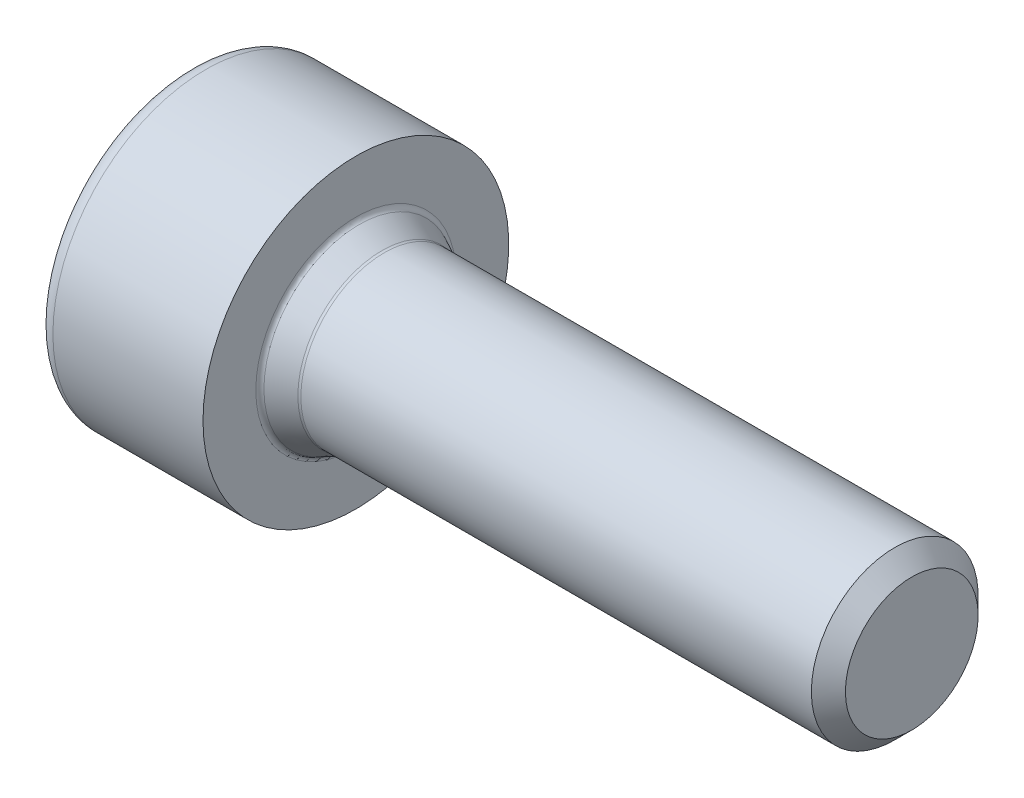
SolidWorks part; units mm, degrees
note: '?' marks a value the reader was unsure of.
ref_plane "前视基准面" through (0, 0, 0) normal (0, 0, 1) x (1, 0, 0)
ref_plane "上视基准面" through (0, 0, 0) normal (0, 1, 0) x (1, 0, 0)
ref_plane "右视基准面" through (0, 0, 0) normal (1, 0, 0) x (0, 0, -1)
sketch "草图1" plane through (0, 0, 0) normal (0, 0, 1) x (1, 0, 0)
  line L0 (-0.4283, 0) -> (-1.15, 1.25)
  line L1 (-1.15, 1.25) -> (-3, 1.25)
  line L2 (-3, 1.25) -> (-3, 2.45)
  line L3 (-2.7, 2.75) -> (0, 2.75)
  line L4 (0, 2.75) -> (0, 1.8)
  line L5 (0.0562, 1.7101) -> (0.4662, 1.5101)
  line L6 (0.51, 1.5) -> (9.6935, 1.5)
  line L7 (9.6935, 1.5) -> (10, 1.1935)
  line L8 (10, 1.1935) -> (10, 0)
  line L9 (10, 0) -> (-0.4283, 0)
  line L10 (10, 0) -> (-0.4283, 0) construction
  arc A0 (-3, 2.45) -> (-2.7, 2.75) centre (-2.7, 2.45) cw
  arc A1 (0, 1.8) -> (0.0562, 1.7101) centre (0.1, 1.8) ccw
  arc A2 (0.4662, 1.5101) -> (0.51, 1.5) centre (0.51, 1.6) ccw
revolve "旋转1" add sketch "草图1" angle 360 about L10
cosmetic thread "装饰螺纹线1" parameters "D1"=1.5, "D2"=2.387
ref_plane "基准面4" through (-1.15, 0, 0) normal (1, 0, 0) x (0, 0, -1)
sketch "草图2" plane through (-1.15, 0, 0) normal (1, 0, 0) x (0, 0, -1)
  line L0 (-1.25, 0.7217) -> (-1.25, -0.7217)
  line L1 (-1.25, -0.7217) -> (0, -1.4434)
  line L2 (0, -1.4434) -> (1.25, -0.7217)
  line L3 (1.25, -0.7217) -> (1.25, 0.7217)
  line L4 (1.25, 0.7217) -> (0, 1.4434)
  line L5 (0, 1.4434) -> (-1.25, 0.7217)
extrude "切除-拉伸1" cut sketch "草图2" against normal blind 2.6
ref_plane "基准面5" through (0, 0, 0) normal (1, 0, 0) x (0, 0, -1)
ref_plane "基准面6" through (10, 0, 0) normal (1, 0, 0) x (0, 0, -1)
ref_plane "基准面7" through (-3, 0, 0) normal (1, 0, 0) x (0, 0, -1)
ref_plane "IP1 XY" through (0, 0, 0) normal (1, 0, 0) x (0, 0, -1)
ref_plane "IP1 XZ" through (0, 0, 0) normal (0, -1, 0) x (-1, 0, 0)
ref_plane "IP1 YZ" through (0, 0, 0) normal (0, 0, -1) x (-1, 0, 0)
ref_axis "IP1 X" through (0, 0, 80.9) along (0, 0, -1)?
ref_axis "IP1 Y" through (0, -50, 0) along (0, 1, 0)?
ref_axis "IP1 Z" through (80.9, 0, 0) along (-1, 0, 0)?
sketch3d "IP1"
  point P0 (0, 0, 0)
ref_plane "IP3 XY" through (10, 0, 0) normal (1, 0, 0) x (0, 0, -1)
ref_plane "IP3 XZ" through (0, 0, 0) normal (0, -1, 0) x (-1, 0, 0)
ref_plane "IP3 YZ" through (0, 0, 0) normal (0, 0, -1) x (-1, 0, 0)
ref_axis "IP3 X" through (10, 0, 80.9) along (0, 0, -1)?
ref_axis "IP3 Y" through (10, -50, 0) along (0, 1, 0)?
ref_axis "IP3 Z" through (80.9, 0, 0) along (-1, 0, 0)?
sketch3d "IP3"
  point P0 (10, 0, 0)
ref_plane "IP2 XY" through (-3, 0, 0) normal (1, 0, 0) x (0, 0, -1)
ref_plane "IP2 XZ" through (0, 0, 0) normal (0, -1, 0) x (-1, 0, 0)
ref_plane "IP2 YZ" through (0, 0, 0) normal (0, 0, -1) x (-1, 0, 0)
ref_axis "IP2 X" through (-3, 0, 80.9) along (0, 0, -1)?
ref_axis "IP2 Y" through (-3, -50, 0) along (0, 1, 0)?
ref_axis "IP2 Z" through (80.9, 0, 0) along (-1, 0, 0)?
sketch3d "IP2"
  point P0 (-3, 0, 0)
ref_plane "IP4 XY" through (0, 0, 0) normal (1, 0, 0) x (0, 0, -1)
ref_plane "IP4 XZ" through (0, 0, 0) normal (0, -1, 0) x (-1, 0, 0)
ref_plane "IP4 YZ" through (0, 0, 0) normal (0, 0, -1) x (-1, 0, 0)
ref_axis "IP4 X" through (0, 0, 80.9) along (0, 0, -1)?
ref_axis "IP4 Y" through (0, -50, 0) along (0, 1, 0)?
ref_axis "IP4 Z" through (80.9, 0, 0) along (-1, 0, 0)?
sketch3d "IP4"
  point P0 (0, 0, 0)
sketch "草图3" plane through (0, 0, 0) normal (1, 0, 0) x (0, 0, -1)
  circle A0 centre (0, 0) radius 2.0625
extrude "凸台-拉伸1" add sketch "草图3" against normal blind 1.5 separate body
other "删除面1" face at (-1.5, 0, -2.0625)
